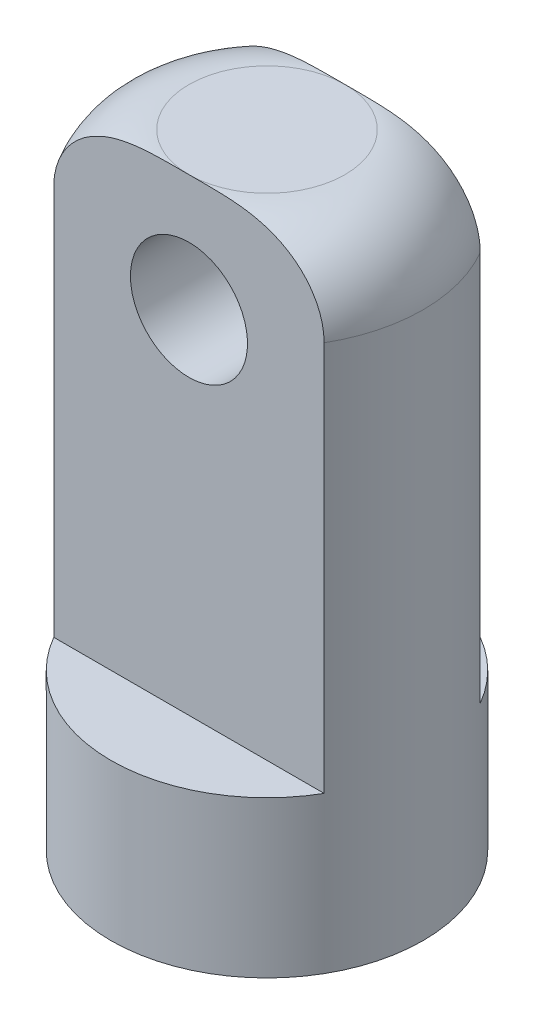
SolidWorks part; units mm, degrees
ref_plane "Front Plane" through (0, 0, 0) normal (0, 0, 1) x (1, 0, 0)
ref_plane "Top Plane" through (0, 0, 0) normal (0, 1, 0) x (1, 0, 0)
ref_plane "Right Plane" through (0, 0, 0) normal (1, 0, 0) x (0, 0, -1)
sketch "Sketch1" plane through (0, 0, 0) normal (0, 1, 0) x (1, 0, 0)
  circle A0 centre (0, 0) radius 20
  dimension "D1" = 40
extrude "Boss-Extrude1" add sketch "Sketch1" along normal blind 80
sketch "Sketch2" plane through (0, 0, 0) normal (1, 0, 0) x (0, 0, -1)
  line L0 (20, 80) -> (-20, 80) construction
  line L1 (-30, 140) -> (-10, 140)
  line L2 (-30, 140) -> (-30, 20)
  line L3 (-30, 20) -> (-10, 20)
  line L4 (-10, 140) -> (-10, 20)
  line L5 (-30, 140) -> (-10, 20) construction
  line L6 (-30, 20) -> (-10, 140) construction
  point P0 (-20, 80)
  dimension "D1" = 10
  dimension "D2" = 60
extrude "Cut-Extrude1" cut sketch "Sketch2" against normal through all both and the other way through all
mirror "Mirror1" about plane through (0, 0, 0) normal (0, 0, 1) of "Cut-Extrude1"
fillet "Fillet1" radius 10 2 edges at (20, 80, 0) (-20, 80, 0)
sketch "Sketch3" plane through (0, 0, 0) normal (0, 0, 1) x (1, 0, 0)
  circle A0 centre (0, 65) radius 7.5
  point P2 (0, 0)
  dimension "D1" = 15
  dimension "D2" = 15
extrude "Cut-Extrude2" cut sketch "Sketch3" against normal through all both and the other way through all
